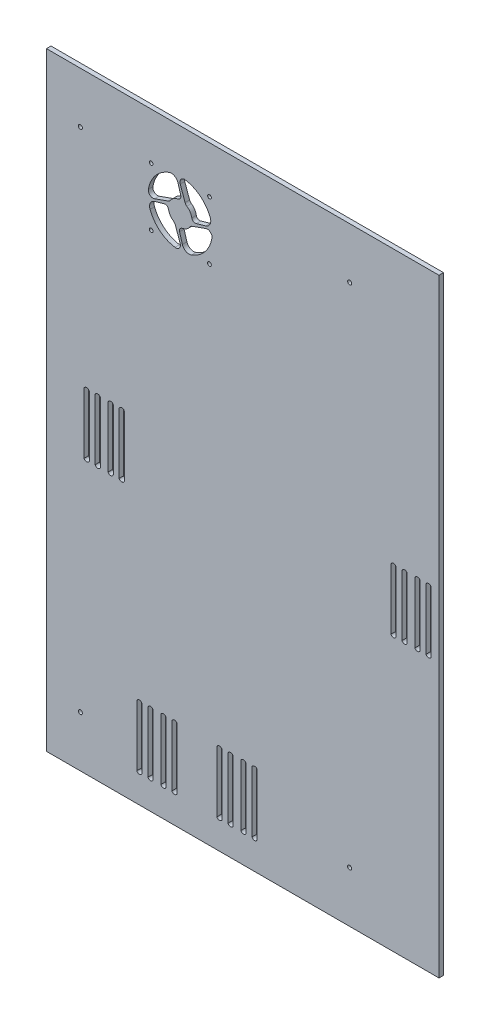
SolidWorks part; units mm, degrees
material "Акрил (Средняя-высокая ударопрочность)"
ref_plane "Front" through (0, 0, 0) normal (0, 0, 1) x (1, 0, 0)
ref_plane "Top" through (0, 0, 0) normal (0, 1, 0) x (1, 0, 0)
ref_plane "Right" through (0, 0, 0) normal (1, 0, 0) x (0, 0, -1)
sketch "Эскиз1" plane through (0, 0, 0) normal (0, 0, 1) x (1, 0, 0)
  line L8 (707.8854, 466.5278) -> (1054.8854, 466.5278)
  line L9 (1054.8854, 466.5278) -> (1054.8854, 1004.5278)
  line L10 (1054.8854, 1004.5278) -> (707.8854, 1004.5278)
  line L11 (707.8854, 1004.5278) -> (707.8854, 466.5278)
  line L12 (1043.3873, 762.4705) -> (1043.3873, 708.585)
  line L13 (1048.0206, 708.585) -> (1048.0206, 762.4705)
  line L16 (1033.58, 762.4705) -> (1033.58, 708.585)
  line L17 (1038.2134, 708.585) -> (1038.2134, 762.4705)
  line L20 (1022.16, 762.3503) -> (1022.16, 708.4647)
  line L21 (1026.7934, 708.4647) -> (1026.7934, 762.3503)
  line L24 (1012.3528, 762.3503) -> (1012.3528, 708.4647)
  line L25 (1016.9861, 708.4647) -> (1016.9861, 762.3503)
  line L28 (889.5351, 545.6892) -> (889.5351, 491.8037)
  line L29 (894.1684, 491.8037) -> (894.1684, 545.6892)
  line L32 (879.7279, 545.6892) -> (879.7279, 491.8037)
  line L33 (884.3612, 491.8037) -> (884.3612, 545.6892)
  line L36 (868.3079, 545.5689) -> (868.3079, 491.6834)
  line L37 (872.9412, 491.6834) -> (872.9412, 545.5689)
  line L40 (858.5006, 545.5689) -> (858.5006, 491.6834)
  line L41 (863.134, 491.6834) -> (863.134, 545.5689)
  line L44 (818.7496, 545.5689) -> (818.7496, 491.6834)
  line L45 (823.3829, 491.6834) -> (823.3829, 545.5689)
  line L48 (808.9424, 545.5689) -> (808.9424, 491.6834)
  line L49 (813.5757, 491.6834) -> (813.5757, 545.5689)
  line L52 (797.5224, 545.4486) -> (797.5224, 491.5631)
  line L53 (802.1557, 491.5631) -> (802.1557, 545.4486)
  line L56 (787.7151, 545.4486) -> (787.7151, 491.5631)
  line L57 (792.3485, 491.5631) -> (792.3485, 545.4486)
  line L60 (825.5733, 923.1011) -> (828, 914.7016)
  line L61 (848.7242, 937.2237) -> (836.7361, 932.9438)
  line L64 (811.8928, 937.788) -> (803.4933, 935.3613)
  line L65 (826.0154, 914.637) -> (821.7354, 926.6251)
  line L68 (826.5912, 951.4525) -> (824.1645, 959.852)
  line L69 (803.4402, 937.3299) -> (815.4283, 941.6098)
  line L72 (840.2601, 936.7816) -> (848.6596, 939.2083)
  line L73 (826.1375, 959.9326) -> (830.4175, 947.9444)
  line L76 (772.1118, 761.4409) -> (772.1118, 707.5554)
  line L77 (776.7451, 707.5554) -> (776.7451, 761.4409)
  line L80 (762.3046, 761.4409) -> (762.3046, 707.5554)
  line L81 (766.9379, 707.5554) -> (766.9379, 761.4409)
  line L84 (750.8846, 761.3206) -> (750.8846, 707.4351)
  line L85 (755.5179, 707.4351) -> (755.5179, 761.3206)
  line L88 (741.0773, 761.3206) -> (741.0773, 707.4351)
  line L89 (745.7107, 707.4351) -> (745.7107, 761.3206)
  circle A2 centre (737.8854, 959.5278) radius 1.8019
  arc A6 (1048.0206, 762.4705) -> (1043.3873, 762.4705) centre (1045.7039, 761.4409) ccw
  arc A7 (1043.3873, 708.585) -> (1048.0206, 708.585) centre (1045.7039, 709.6147) ccw
  arc A10 (1038.2134, 762.4705) -> (1033.58, 762.4705) centre (1035.8967, 761.4409) ccw
  arc A11 (1033.58, 708.585) -> (1038.2134, 708.585) centre (1035.8967, 709.6147) ccw
  arc A14 (1026.7934, 762.3503) -> (1022.16, 762.3503) centre (1024.4767, 761.3206) ccw
  arc A15 (1022.16, 708.4647) -> (1026.7934, 708.4647) centre (1024.4767, 709.4944) ccw
  arc A18 (1016.9861, 762.3503) -> (1012.3528, 762.3503) centre (1014.6695, 761.3206) ccw
  arc A19 (1012.3528, 708.4647) -> (1016.9861, 708.4647) centre (1014.6695, 709.4944) ccw
  circle A20 centre (975.8854, 511.5278) radius 1.8019
  arc A24 (894.1684, 545.6892) -> (889.5351, 545.6892) centre (891.8518, 544.6596) ccw
  arc A25 (889.5351, 491.8037) -> (894.1684, 491.8037) centre (891.8518, 492.8333) ccw
  arc A28 (884.3612, 545.6892) -> (879.7279, 545.6892) centre (882.0445, 544.6596) ccw
  arc A29 (879.7279, 491.8037) -> (884.3612, 491.8037) centre (882.0445, 492.8333) ccw
  arc A32 (872.9412, 545.5689) -> (868.3079, 545.5689) centre (870.6245, 544.5393) ccw
  arc A33 (868.3079, 491.6834) -> (872.9412, 491.6834) centre (870.6245, 492.713) ccw
  arc A36 (863.134, 545.5689) -> (858.5006, 545.5689) centre (860.8173, 544.5393) ccw
  arc A37 (858.5006, 491.6834) -> (863.134, 491.6834) centre (860.8173, 492.713) ccw
  arc A40 (823.3829, 545.5689) -> (818.7496, 545.5689) centre (821.0662, 544.5393) ccw
  arc A41 (818.7496, 491.6834) -> (823.3829, 491.6834) centre (821.0662, 492.713) ccw
  arc A44 (813.5757, 545.5689) -> (808.9424, 545.5689) centre (811.259, 544.5393) ccw
  arc A45 (808.9424, 491.6834) -> (813.5757, 491.6834) centre (811.259, 492.713) ccw
  arc A48 (802.1557, 545.4486) -> (797.5224, 545.4486) centre (799.839, 544.419) ccw
  arc A49 (797.5224, 491.5631) -> (802.1557, 491.5631) centre (799.839, 492.5927) ccw
  arc A52 (792.3485, 545.4486) -> (787.7151, 545.4486) centre (790.0318, 544.419) ccw
  arc A53 (787.7151, 491.5631) -> (792.3485, 491.5631) centre (790.0318, 492.5927) ccw
  circle A54 centre (737.8854, 511.5278) radius 1.8019
  circle A56 centre (975.8854, 959.5278) radius 1.8019
  circle A58 centre (851.969, 911.6958) radius 1.6474
  circle A60 centre (800.4875, 911.6958) radius 1.6474
  circle A62 centre (851.969, 963.1773) radius 1.6474
  circle A64 centre (800.4875, 963.1773) radius 1.6474
  arc A72 (836.1108, 910.6343) -> (854.1736, 932.681) centre (826.088, 937.2688) ccw
  arc A73 (828, 914.7016) -> (836.1108, 910.6343) centre (833.935, 916.4163) ccw
  arc A74 (827.9791, 926.9958) -> (825.5733, 923.1011) centre (828.5408, 923.9585) ccw
  arc A75 (827.9791, 926.9958) -> (834.719, 931.3866) centre (826.0764, 937.2848) ccw
  arc A76 (836.7361, 932.9438) -> (834.719, 931.3866) centre (838.1209, 929.065) ccw
  arc A77 (854.1736, 932.681) -> (848.7242, 937.2237) centre (850.109, 933.345) ccw
  arc A84 (799.426, 927.2504) -> (821.4727, 909.1876) centre (826.0605, 937.2732) ccw
  arc A85 (803.4933, 935.3613) -> (799.426, 927.2504) centre (805.2079, 929.4262) ccw
  arc A86 (815.7875, 935.3821) -> (811.8928, 937.788) centre (812.7501, 934.8204) ccw
  arc A87 (815.7875, 935.3821) -> (820.1783, 928.6422) centre (826.0764, 937.2848) ccw
  arc A88 (821.7354, 926.6251) -> (820.1783, 928.6422) centre (817.8567, 925.2404) ccw
  arc A89 (821.4727, 909.1876) -> (826.0154, 914.637) centre (822.1366, 913.2522) ccw
  arc A96 (816.0536, 963.9193) -> (797.9908, 941.8726) centre (826.0764, 937.2848) ccw
  arc A97 (824.1645, 959.852) -> (816.0536, 963.9193) centre (818.2294, 958.1373) ccw
  arc A98 (824.1853, 947.5577) -> (826.5912, 951.4525) centre (823.6236, 950.5951) ccw
  arc A99 (824.1853, 947.5577) -> (817.4454, 943.167) centre (826.088, 937.2688) ccw
  arc A100 (815.4283, 941.6098) -> (817.4454, 943.167) centre (814.0436, 945.4886) ccw
  arc A101 (797.9908, 941.8726) -> (803.4402, 937.3299) centre (802.0554, 941.2086) ccw
  arc A110 (852.7269, 947.3192) -> (830.6802, 965.382) centre (826.0924, 937.2963) ccw
  arc A111 (848.6596, 939.2083) -> (852.7269, 947.3192) centre (846.945, 945.1434) ccw
  arc A112 (836.3654, 939.1875) -> (840.2601, 936.7816) centre (839.4028, 939.7491) ccw
  arc A113 (836.3654, 939.1875) -> (831.9746, 945.9274) centre (826.0764, 937.2848) ccw
  arc A114 (830.4175, 947.9444) -> (831.9746, 945.9274) centre (834.2962, 949.3292) ccw
  arc A115 (830.6802, 965.382) -> (826.1375, 959.9326) centre (830.0163, 961.3173) ccw
  arc A116 (776.7451, 761.4409) -> (772.1118, 761.4409) centre (774.4285, 760.4113) ccw
  arc A117 (772.1118, 707.5554) -> (776.7451, 707.5554) centre (774.4285, 708.585) ccw
  arc A120 (766.9379, 761.4409) -> (762.3046, 761.4409) centre (764.6212, 760.4113) ccw
  arc A121 (762.3046, 707.5554) -> (766.9379, 707.5554) centre (764.6212, 708.585) ccw
  arc A124 (755.5179, 761.3206) -> (750.8846, 761.3206) centre (753.2012, 760.291) ccw
  arc A125 (750.8846, 707.4351) -> (755.5179, 707.4351) centre (753.2012, 708.4647) ccw
  arc A128 (745.7107, 761.3206) -> (741.0773, 761.3206) centre (743.394, 760.291) ccw
  arc A129 (741.0773, 707.4351) -> (745.7107, 707.4351) centre (743.394, 708.4647) ccw
  dimension "D1" = 538
  dimension "D2" = 347
extrude "Бобышка-Вытянуть1" add sketch "Эскиз1" along normal blind 4
